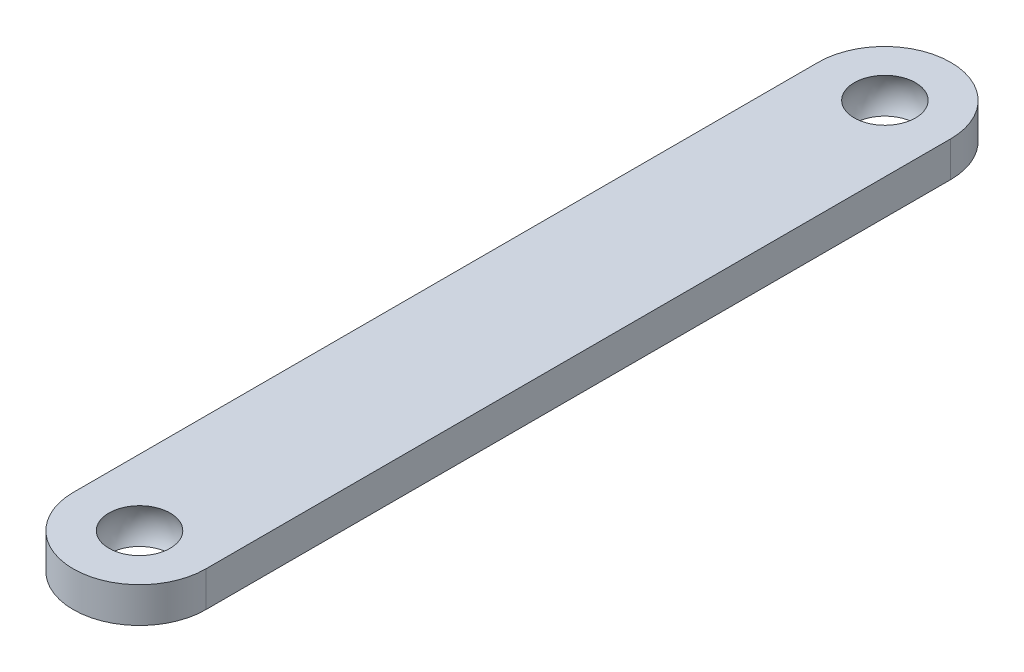
SolidWorks part; units mm, degrees
material "ABS"
ref_plane "Front Plane" through (0, 0, 0) normal (0, 0, 1) x (1, 0, 0)
ref_plane "Top Plane" through (0, 0, 0) normal (0, 1, 0) x (1, 0, 0)
ref_plane "Right Plane" through (0, 0, 0) normal (1, 0, 0) x (0, 0, -1)
sketch "Sketch1" plane through (0, 0, 0) normal (0, 1, 0) x (1, 0, 0)
  line L0 (0, 53.5432) -> (0, 0) construction
  line L1 (4.7625, 53.5432) -> (4.7625, 0)
  line L2 (-4.7625, 53.5432) -> (-4.7625, 0)
  circle A0 centre (0, 0) radius 1.5875
  circle A1 centre (0, 53.5432) radius 1.5875
  arc A2 (4.7625, 53.5432) -> (-4.7625, 53.5432) centre (0, 53.5432) ccw
  arc A3 (-4.7625, 0) -> (4.7625, 0) centre (0, 0) ccw
  point P5 (0, 26.7716)
  dimension "D1" = 3.175
  dimension "D2" = 3.175
  dimension "D3" = 53.5432
  dimension "D4" = 9.525
extrude "Boss-Extrude1" add sketch "Sketch1" along normal mid plane 2.54
sketch "Sketch2" plane through (0, 0, 0) normal (1, 0, 0) x (0, 0, -1)
  line L0 (0, -2.54) -> (0, 2.54)
  arc A0 (0, 2.54) -> (0, -2.54) centre (0, 0) cw
  dimension "D1" = 2.54
revolve "Cut-Revolve1" cut sketch "Sketch2" angle 360 about L0
sketch "Sketch3" plane through (0, 0, 0) normal (1, 0, 0) x (0, 0, -1)
  line L0 (55.1307, 1.27) -> (51.9557, 1.27) construction
  line L5 (53.5745, 8.5087) -> (53.5745, -3.7708)
  arc A0 (53.5745, 2.54) -> (53.5745, -2.54) centre (53.5745, 0) ccw
  point P0 (53.5745, 1.27)
  point P8 (0, 0)
  dimension "D1" = 2.54
revolve "Cut-Revolve2" cut sketch "Sketch3" angle 360 about L5 region at (0, 0, -52.4965)
